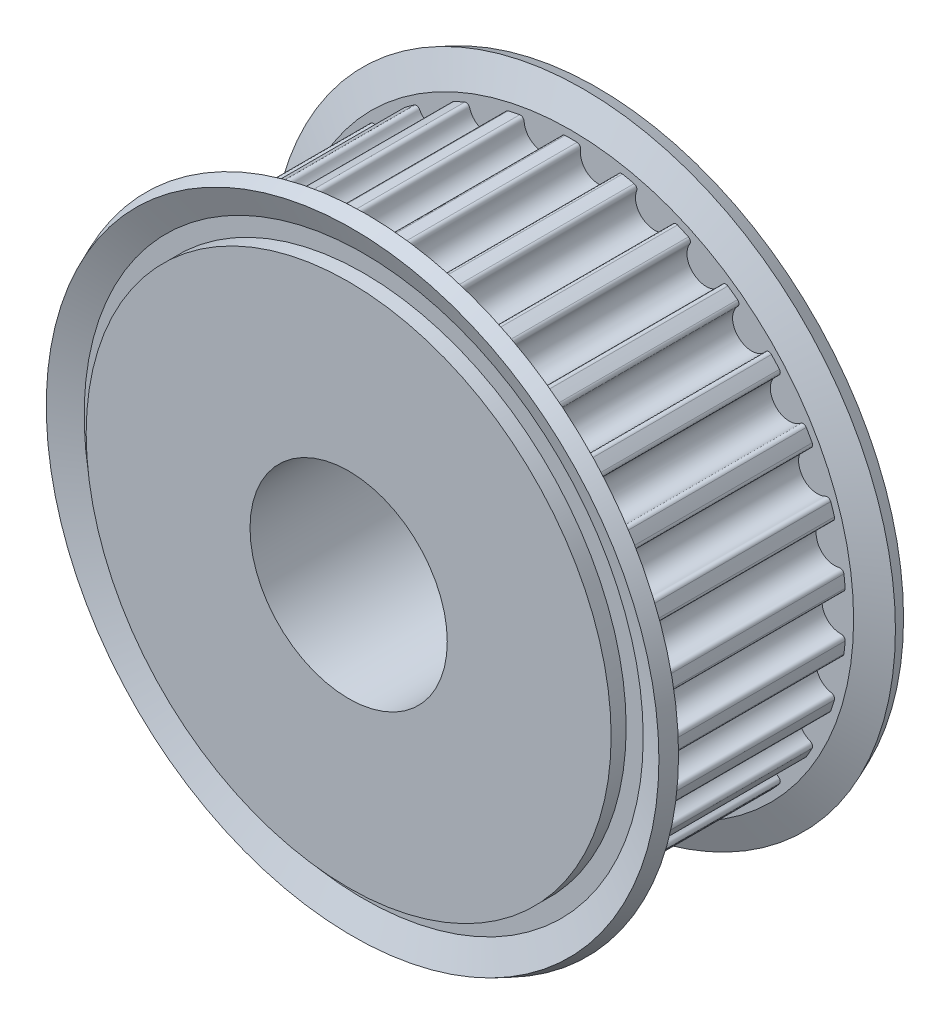
SolidWorks part; units mm, degrees
ref_plane "前视基准面" through (0, 0, 0) normal (0, 0, 1) x (1, 0, 0)
ref_plane "上视基准面" through (0, 0, 0) normal (0, 1, 0) x (1, 0, 0)
ref_plane "右视基准面" through (0, 0, 0) normal (1, 0, 0) x (0, 0, -1)
ref_axis "基准轴1" through (0, 0, 55) along (0, 0, -1)
sketch "SketchRevolveGearBelt01" plane through (0, 0, 0) normal (1, 0, 0) x (0, 0, -1)
  line L0 (0, 0) -> (1, 0) construction
  line L1 (6.4008, 0) -> (6.4008, 13.3069)
  line L2 (6.4008, 13.3069) -> (5.6388, 13.3069)
  line L3 (5.6388, 13.3069) -> (5.6388, 14.1713)
  line L4 (5.6388, 14.1713) -> (6.2015, 15.5299)
  line L5 (6.2015, 15.5299) -> (5.4975, 15.8215)
  line L6 (5.4975, 15.8215) -> (4.8768, 14.3229)
  line L7 (4.8768, 14.3229) -> (4.8768, 13.9419)
  line L8 (4.8768, 13.9419) -> (-4.8768, 13.9419)
  line L9 (-4.8768, 13.9419) -> (-4.8768, 14.3229)
  line L10 (-4.8768, 14.3229) -> (-5.4975, 15.8215)
  line L11 (-5.4975, 15.8215) -> (-6.2015, 15.5299)
  line L12 (-6.2015, 15.5299) -> (-5.6388, 14.1713)
  line L13 (-5.6388, 14.1713) -> (-5.6388, 13.3069)
  line L14 (-5.6388, 13.3069) -> (-6.4008, 13.3069)
  line L15 (-6.4008, 13.3069) -> (-6.4008, 0)
  line L16 (-6.4008, 0) -> (6.4008, 0)
  dimension "GearBeltFlange1OutsideLength" = 0.8644
  dimension "GearBeltFlange1X" = 0.5627
  dimension "GearBeltFlange1Y" = 1.3586
  dimension "GearBeltFlangeThickness" = 0.762
  dimension "GearBeltFlangeInside" = 0.381
  dimension "GearBeltOutsideDiameter" = 13.9419
  dimension "GearBeltFlange2X" = 0.5627
revolve "GearBelt01" add sketch "SketchRevolveGearBelt01" angle 360 about L0
sketch "SketchToothGearBelt01" plane through (0, 0, 0) normal (0, 0, 1) x (1, 0, 0)
  arc A0 (13.8935, 1.162) -> (13.8935, -1.162) centre (0, 0) cw
  spline S0 degree 3 poles (13.8935, -1.162) (13.8944, -1.1516) (13.8944, -1.1357) (13.8918, -1.1148) (13.8886, -1.0994) (13.8841, -1.0843) (13.8784, -1.0695) (13.8714, -1.0553) (13.8634, -1.0418) (13.8542, -1.0289) (13.844, -1.0168) (13.8329, -1.0057) (13.8209, -0.9954) (13.808, -0.9862) (13.7945, -0.9781) (13.7803, -0.9712) (13.7656, -0.9654) (13.7505, -0.9609) (13.735, -0.9576) (13.7194, -0.9556) (13.6903, -0.9547) (13.6423, -0.9556) (13.5752, -0.953) (13.503, -0.9442) (13.4317, -0.9299) (13.3617, -0.91) (13.2935, -0.8847) (13.2275, -0.8541) (13.1641, -0.8184) (13.1036, -0.7779) (13.0466, -0.7328) (12.9932, -0.6834) (12.9439, -0.6299) (12.8989, -0.5727) (12.8585, -0.5122) (12.8231, -0.4487) (12.7926, -0.3826) (12.7675, -0.3143) (12.7478, -0.2443) (12.7336, -0.1729) (12.725, -0.1007) (12.7231, -0.0476) (12.7232, -0.014) (12.7232, 0) (12.7232, 0.014) (12.7231, 0.0476) (12.725, 0.1007) (12.7336, 0.1729) (12.7478, 0.2443) (12.7675, 0.3143) (12.7926, 0.3826) (12.8231, 0.4487) (12.8585, 0.5122) (12.8989, 0.5727) (12.9439, 0.6299) (12.9932, 0.6834) (13.0466, 0.7328) (13.1036, 0.7779) (13.1641, 0.8184) (13.2275, 0.8541) (13.2935, 0.8847) (13.3617, 0.91) (13.4317, 0.9299) (13.503, 0.9442) (13.5752, 0.953) (13.6423, 0.9556) (13.6903, 0.9547) (13.7194, 0.9556) (13.735, 0.9576) (13.7505, 0.9609) (13.7656, 0.9654) (13.7803, 0.9712) (13.7945, 0.9781) (13.808, 0.9862) (13.8209, 0.9954) (13.8329, 1.0057) (13.844, 1.0168) (13.8542, 1.0289) (13.8634, 1.0418) (13.8714, 1.0553) (13.8784, 1.0695) (13.8841, 1.0843) (13.8886, 1.0994) (13.8918, 1.1148) (13.8944, 1.1357) (13.8944, 1.1516) (13.8935, 1.162) knots 0 0 0 0 0.008513 0.012769 0.017025 0.021281 0.025538 0.029794 0.03405 0.038306 0.042563 0.046819 0.051075 0.055331 0.059588 0.063844 0.0681 0.072356 0.076613 0.080869 0.085125 0.100157 0.119771 0.139386 0.159 0.178614 0.198229 0.217843 0.237457 0.257071 0.276686 0.2963 0.315914 0.335529 0.355143 0.374757 0.394372 0.413986 0.4336 0.453214 0.472829 0.492443 0.496222 0.5 0.503778 0.507557 0.527171 0.546786 0.5664 0.586014 0.605628 0.625243 0.644857 0.664471 0.684086 0.7037 0.723314 0.742929 0.762543 0.782157 0.801771 0.821386 0.841 0.860614 0.880229 0.899843 0.914875 0.919131 0.923387 0.927644 0.9319 0.936156 0.940412 0.944669 0.948925 0.953181 0.957437 0.961694 0.96595 0.970206 0.974462 0.978719 0.982975 0.987231 0.991487 1 1 1 1
extrude "ToothExtrudeCutGearBelt01" cut sketch "SketchToothGearBelt01" against normal blind 4.8768 and the other way blind 4.8768
pattern_circular "PatternGearBelt01" count 30 every 12 about axis through (0, 0, 55) along (0, 0, -1) of "ToothExtrudeCutGearBelt01"
sketch "BoreRevolveSketch" plane through (0, 0, 0) normal (1, 0, 0) x (0, 0, -1)
  line L0 (0, 0) -> (1, 0) construction
  line L1 (-6.4008, 0) -> (6.4008, 0)
  line L2 (6.4008, 0) -> (6.4008, 5)
  line L3 (6.4008, 5) -> (-6.4008, 5)
  line L4 (-6.4008, 5) -> (-6.4008, 0)
  dimension "TaperSide1" = 5
  dimension "TaperSide2" = 5
revolve "BoreRevolveCut" cut sketch "BoreRevolveSketch" angle 360 about L0
sketch "AuxiliarySketchGearBelt01" plane through (0, 0, 0) normal (0, 0, 1) x (1, 0, 0)
  circle A0 centre (0, 0) radius 14.3229 construction
  dimension "PitchDiameter" = 28.6458
